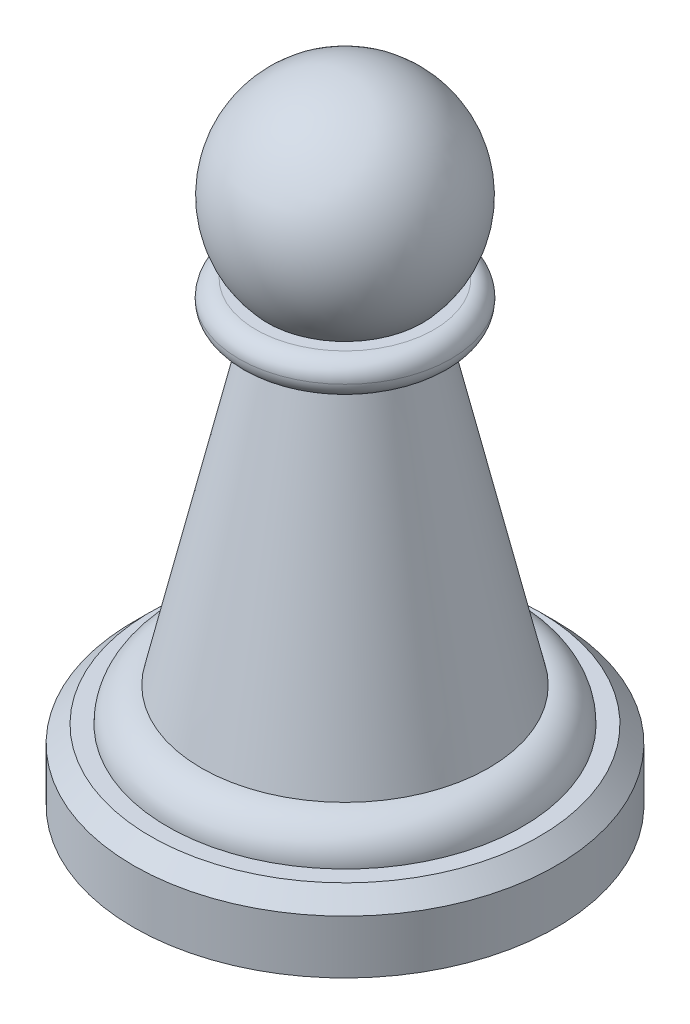
SolidWorks part; units mm, degrees
ref_plane "Front Plane" through (0, 0, 0) normal (0, 0, 1) x (1, 0, 0)
ref_plane "Top Plane" through (0, 0, 0) normal (0, 1, 0) x (1, 0, 0)
ref_plane "Right Plane" through (0, 0, 0) normal (1, 0, 0) x (0, 0, -1)
sketch "Sketch1" plane through (0, 0, 0) normal (0, 0, 1) x (1, 0, 0)
  line L0 (0, 0) -> (0, 28.575) construction
  line L1 (-6.477, 3.175) -> (-6.477, 4.699) construction
  line L2 (0, 0) -> (-9.525, 0)
  line L4 (-8.001, 3.175) -> (-9.525, 3.175)
  line L5 (-9.525, 0) -> (-9.525, 3.175)
  line L8 (-6.477, 4.699) -> (-8.001, 4.699)
  line L9 (-8.001, 3.175) -> (-8.001, 4.699)
  line L10 (-3.175, 19.05) -> (-9.525, 19.05) construction
  line L11 (-6.477, 4.699) -> (-3.175, 19.05)
  line L12 (0, 19.05) -> (-9.525, 19.05) construction
  line L13 (-3.175, 19.05) -> (-4.7752, 19.05)
  line L15 (-3.4919, 20.574) -> (-4.7752, 20.574)
  line L16 (-4.7752, 19.05) -> (-4.7752, 20.574)
  line L17 (0, 0) -> (0, 28.575)
  arc A0 (0, 28.575) -> (-3.4919, 20.574) centre (0, 23.8125) ccw
  dimension "D9" = 9.525
  dimension "D1" = 28.575
  dimension "D2" = 9.525
  dimension "D3" = 3.175
  dimension "D4" = 1.524
  dimension "D5" = 1.524
  dimension "D6" = 3.175
  dimension "D7" = 1.524
revolve "Revolve1" add sketch "Sketch1" angle 360 about L17
chamfer "Chamfer1" distance 0.762 angle 45 1 edges at (0, 3.175, -9.525)
fillet "Fillet2" radius 1.524 1 edges at (0, 4.699, -8.001)
fillet "Fillet3" radius 0.762 2 edges at (0, 20.574, -4.7752) (0, 19.05, -4.7752)
